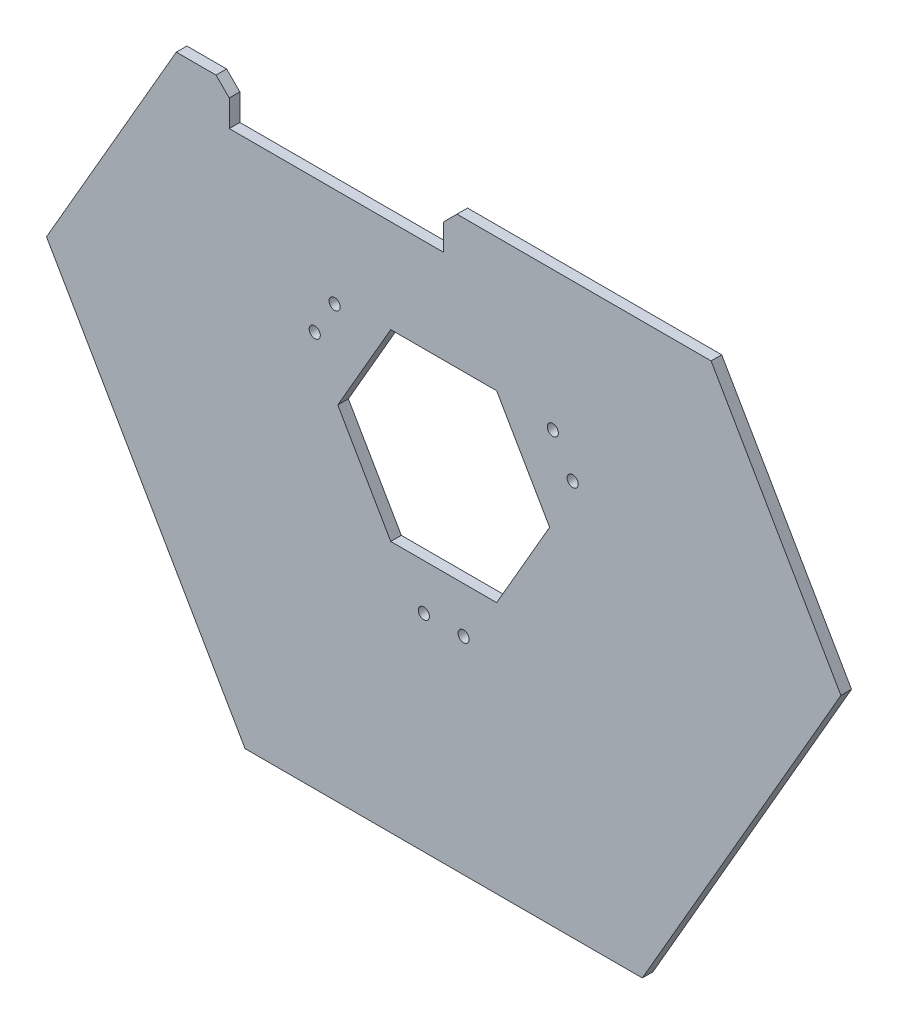
SolidWorks part; units mm, degrees
material "5052-O"
ref_plane "前基準面" through (0, 0, 0) normal (0, 0, 1) x (1, 0, 0)
ref_plane "上基準面" through (0, 0, 0) normal (0, 1, 0) x (1, 0, 0)
ref_plane "右基準面" through (0, 0, 0) normal (1, 0, 0) x (0, 0, -1)
sketch "草圖1" plane through (0, 0, 0) normal (0, 0, 1) x (1, 0, 0)
  line L1 (150, 0) -> (75, 129.9038)
  line L2 (75, 129.9038) -> (-75, 129.9038)
  line L3 (-75, 129.9038) -> (-150, 0)
  line L4 (-150, 0) -> (-75, -129.9038)
  line L5 (-75, -129.9038) -> (75, -129.9038)
  line L6 (75, -129.9038) -> (150, 0)
  circle A0 centre (0, 0) radius 129.9038 construction
  point P1 (0, 0)
  dimension "D1" = 150
extrude "填料-伸長1" add sketch "草圖1" along normal blind 4
ref_axis "基準軸1" through (0, 0, 0) along (0, 0, 1)
sketch "草圖2" plane through (0, 0, 4) normal (0, 0, 1) x (1, 0, 0)
  line L0 (-7.5, -51.9038) -> (7.5, -51.9038) construction
  line L1 (-75, -129.9038) -> (75, -129.9038) construction
  circle A0 centre (-7.5, -51.9038) radius 2.1
  circle A1 centre (7.5, -51.9038) radius 2.1
  point P4 (0, -51.9038)
  dimension "D1" = 4.2
  dimension "D2" = 4.2
  dimension "D3" = 78
  dimension "D4" = 15
extrude "除料-伸長1" cut sketch "草圖2" against normal up to next
sketch "草圖3" plane through (0, 0, 4) normal (0, 0, 1) x (1, 0, 0)
  line L0 (-100.9808, 84.9038) -> (-80.9808, 84.9038)
  line L1 (-75, 129.9038) -> (-150, 0) construction
  line L2 (-80.9808, 84.9038) -> (-80.9808, 69.9038)
  line L3 (-80.9808, 69.9038) -> (0, 69.9038)
  line L4 (0, 69.9038) -> (0, 84.9038)
  line L5 (0, 84.9038) -> (100.9808, 84.9038)
  line L6 (150, 0) -> (75, 129.9038) construction
  line L7 (75, 129.9038) -> (-75, 129.9038) construction
  point P12 (0, 0)
  point P13 (0, 0)
  point P14 (-88.7457, 92.2243)
  point P15 (0, 0)
  point P16 (0, 129.9038)
  dimension "D1" = 60
  dimension "D2" = 15
  dimension "D4" = 20
extrude "除料-伸長2" cut sketch "草圖3" against normal blind 4 and the other way through all
sketch "草圖4" plane through (0, 0, 4) normal (0, 0, 1) x (1, 0, 0)
  line L1 (40, 0) -> (20, 34.641)
  line L2 (20, 34.641) -> (-20, 34.641)
  line L3 (-20, 34.641) -> (-40, 0)
  line L4 (-40, 0) -> (-20, -34.641)
  line L5 (-20, -34.641) -> (20, -34.641)
  line L6 (20, -34.641) -> (40, 0)
  circle A0 centre (0, 0) radius 34.641 construction
  point P1 (0, 0)
  dimension "D1" = 40
extrude "除料-伸長3" cut sketch "草圖4" against normal up to next
pattern_circular "環狀複製排列1" count 3 over 360 about axis through (0, 0, 0) along (0, 0, 1) of "除料-伸長1"
chamfer "導角1" distance 5 angle 45 2 edges at (0, 84.9038, 2) (-80.9808, 84.9038, 2)
